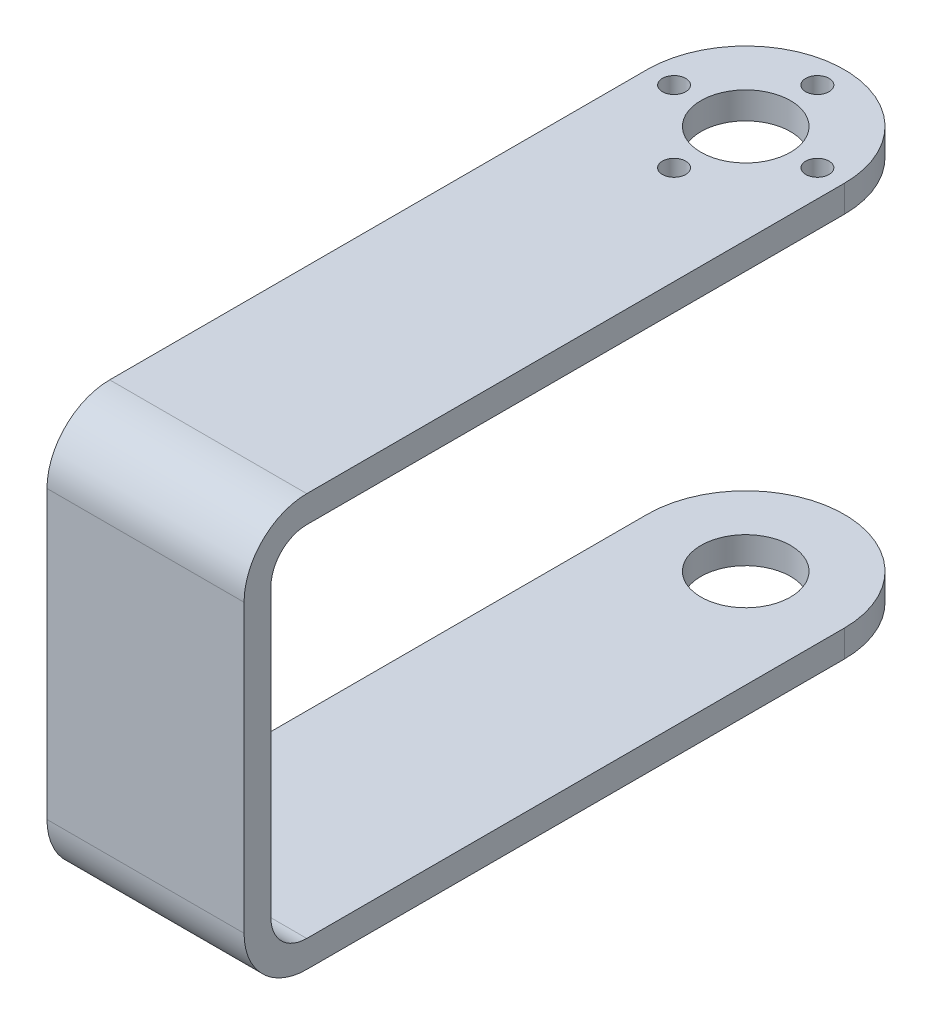
SolidWorks part; units mm, degrees
ref_plane "Front Plane" through (0, 0, 0) normal (0, 0, 1) x (1, 0, 0)
ref_plane "Top Plane" through (0, 0, 0) normal (0, 1, 0) x (1, 0, 0)
ref_plane "Right Plane" through (0, 0, 0) normal (1, 0, 0) x (0, 0, -1)
sketch "Sketch1" plane through (0, 0, 0) normal (0, 1, 0) x (1, 0, 0)
  line L5 (-11, 0) -> (11, 0)
  line L6 (-11, 0) -> (-11, -60)
  line L7 (-11, -60) -> (11, -60)
  line L8 (11, 0) -> (11, -60)
  circle A0 centre (0, 0) radius 11
  circle A1 centre (0, 0) radius 8 construction
  circle A2 centre (0, 8) radius 1.3
  circle A3 centre (8, 0) radius 1.3
  circle A4 centre (0, -8) radius 1.3
  circle A5 centre (-8, 0) radius 1.3
  circle A6 centre (0, 0) radius 5
  point P19 (0, 0)
  dimension "D1" = 16
  dimension "D3" = 2.6
  dimension "D4" = 10
  dimension "D5" = 22
  dimension "D6" = 22
  dimension "D7" = 60
  dimension "D2" = 4
extrude "Boss-Extrude1" add sketch "Sketch1" along normal blind 3 contours A0 L6 L7 L8 | A6 L5 A5 A0 A3 A4 | A6 L5 A3 A0 A5 A2 region at (0, 0, -5.4117) region at (0, 0, 5.4117) region at (0, 0, 34.261)
sketch "Sketch2" plane through (11, 0, 0) normal (1, 0, 0) x (0, 0, -1)
  line L0 (-60, 3) -> (-60, 0)
  line L1 (-67, -4) -> (-64, -4)
  line L2 (-67, -4) -> (-67, -36)
  line L3 (-67, -36) -> (-64, -36)
  line L4 (-64, -4) -> (-64, -36)
  line L5 (-60, -40) -> (-60, -43)
  arc A0 (-60, 0) -> (-64, -4) centre (-60, -4) ccw
  arc A1 (-60, 3) -> (-67, -4) centre (-60, -4) ccw
  arc A2 (-67, -36) -> (-60, -43) centre (-60, -36) ccw
  arc A3 (-64, -36) -> (-60, -40) centre (-60, -36) ccw
  point P12 (0, 0)
  point P13 (0, 0)
  line M4 (-60, 3) -> (-60, 0)
  dimension "D1" = 4
  dimension "D2" = 4
  dimension "D3" = 4
  dimension "D4" = 4
  dimension "D5" = 32
extrude "Boss-Extrude2" add sketch "Sketch2" against normal up to surface (22 mm away) contours L4 L1 L2 L3 | A1 L1 A0 M4 | A3 L3 A2 L5 region at (11, -0.4118, 63.5882) region at (11, -20, 65.5) region at (11, -39.5882, 63.5882) up to face at (-11, 1.5, 30)
ref_plane "Plane1" through (0, -40, 0) normal (0, -1, 0) x (-1, 0, 0)
sketch "Sketch6" plane through (0, -40, 0) normal (0, -1, 0) x (-1, 0, 0)
  line L1 (-11, 0) -> (11, 0)
  line L2 (-11, 0) -> (-11, -60)
  line L3 (-11, -60) -> (11, -60)
  line L4 (11, 0) -> (11, -60)
  circle A1 centre (0, 0) radius 11
  circle A2 centre (0, 0) radius 5
extrude "Boss-Extrude3" add sketch "Sketch6" along normal blind 3 contours A1 L2 L3 L4 | A2 L1 A1 | A2 L1 A1 region at (0, -40, -5.3317) region at (0, -40, 5.3317) region at (0, -40, 34.261)
equation "\"D6@Sketch1\"=\"D5@Sketch1\""
